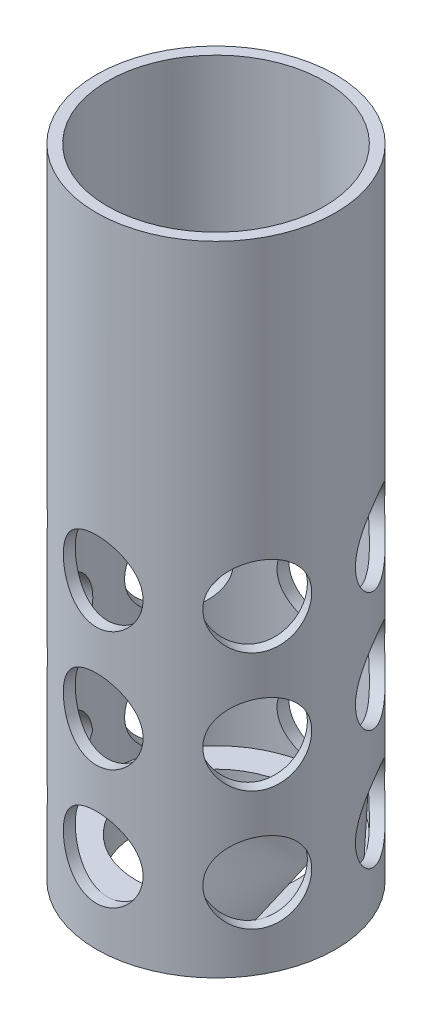
SolidWorks part; units mm, degrees
ref_plane "Front Plane" through (0, 0, 0) normal (0, 0, 1) x (1, 0, 0)
ref_plane "Top Plane" through (0, 0, 0) normal (0, 1, 0) x (1, 0, 0)
ref_plane "Right Plane" through (0, 0, 0) normal (1, 0, 0) x (0, 0, -1)
sketch "Sketch1" plane through (0, 0, 0) normal (0, 0, 1) x (1, 0, 0)
  line L0 (-8.636, 0) -> (-9.525, 0)
  line L1 (-9.525, 0) -> (-9.525, -50.8)
  line L2 (-9.525, -50.8) -> (-6.35, -50.8)
  line L3 (-6.35, -50.8) -> (-6.35, -47.625)
  line L4 (-6.35, -47.625) -> (-8.636, -47.625)
  line L5 (-8.636, -47.625) -> (-8.636, 0)
  line L6 (0, 0) -> (0, -30.0814) construction
  dimension "D1" = 6.35
  dimension "D2" = 9.525
  dimension "D3" = 0.889
  dimension "D4" = 50.8
  dimension "D5" = 3.175
revolve "Revolve1" add sketch "Sketch1" angle 360 about L6
ref_plane "Plane1" through (0, 0, 9.525) normal (0, 0, 1) x (1, 0, 0)
hole_wizard "1/4 (0.25) Diameter Hole1" positions "Sketch2" profile "Sketch4" hole size "1/4" standard "ANSI Inch" end condition through all
sketch "Sketch2" plane through (0, 0, 9.525) normal (0, 0, 1) x (1, 0, 0)
  point P0 (0, -44.45)
  dimension "D1" = 44.45
sketch "Sketch4" plane through (0, -44.45, 9.525) normal (1, 0, 0) x (0, -1, 0)
  line L0 (0, 0) -> (0, 19.05)
  line L1 (0, 19.05) -> (3.175, 19.05)
  line L2 (3.175, 19.05) -> (3.175, 0)
  line L5 (3.175, 0) -> (0, 0)
  line L11 (0, -6.35) -> (0, 107.95) construction
  dimension "Thru Hole Dia." = 6.35
  dimension "Thru Hole Depth" = 19.05
ref_axis "Axis1" through (0, -53.34, 0) along (0, 1, 0)
pattern_circular "CirPattern1" count 6 over 360 about axis through (0, -53.34, 0) along (0, 1, 0) of "1/4 (0.25) Diameter Hole1"
pattern_linear "LPattern1" count 3 spacing 9.525 along (0, 1, 0) of "CirPattern1"
